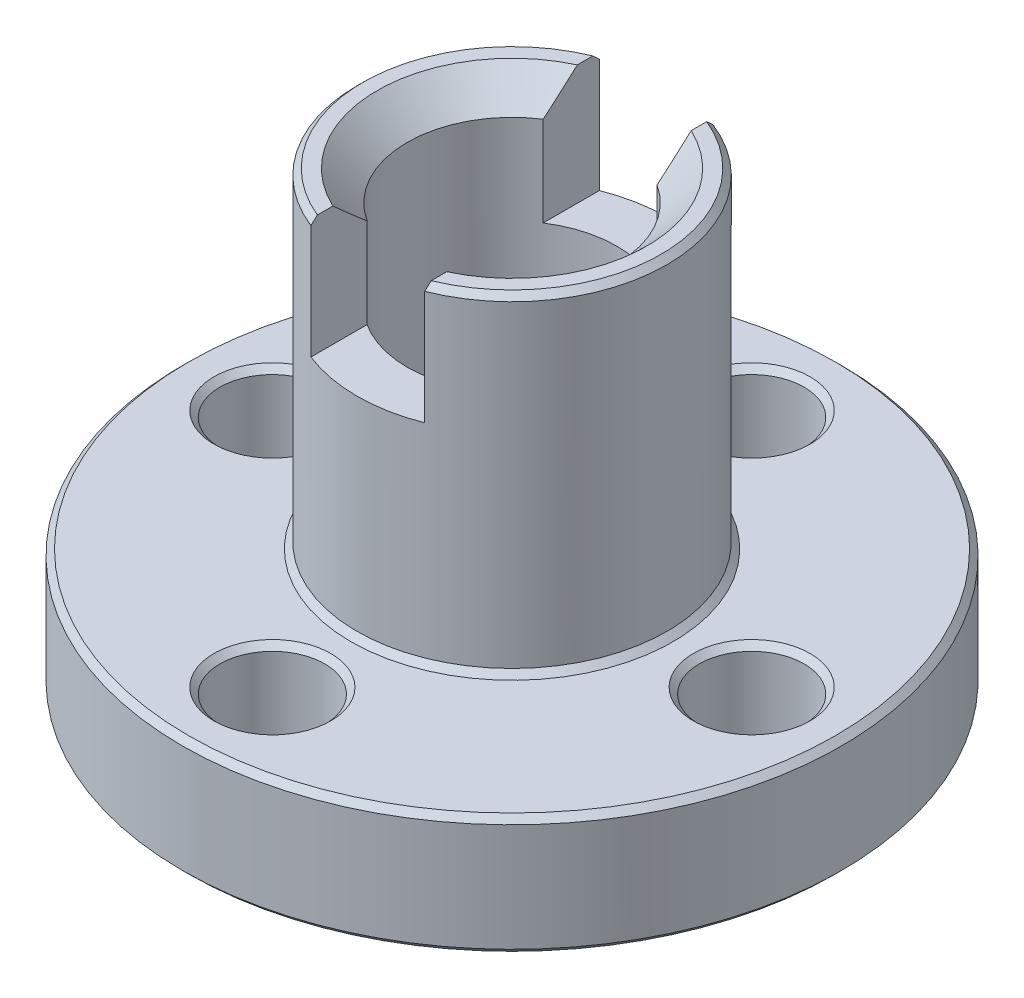
SolidWorks part; units mm, degrees
material "Латунь"
ref_plane "Спереди" through (0, 0, 0) normal (0, 0, 1) x (1, 0, 0)
ref_plane "Сверху" through (0, 0, 0) normal (0, 1, 0) x (1, 0, 0)
ref_plane "Справа" through (0, 0, 0) normal (1, 0, 0) x (0, 0, -1)
sketch "Эскиз2" plane through (0, 0, 0) normal (1, 0, 0) x (0, 0, -1)
  line L0 (0, 0) -> (11, 0)
  line L1 (11, 0) -> (11, 4)
  line L2 (11, 4) -> (5.175, 4)
  line L3 (5.175, 4) -> (5.175, 15)
  line L4 (5.175, 15) -> (0, 15)
  line L5 (0, 15) -> (0, 0)
  line L6 (0, 40.8158) -> (0, -22.7526) construction
  line L7 (3.5, 15) -> (3.5, 0)
  dimension "D1" = 22
  dimension "D2" = 4
  dimension "D3" = 10.35
  dimension "D4" = 15
  dimension "D5" = 7
revolve "Повернуть1" add sketch "Эскиз2" angle 360 about L6 region at (0, 7.5, -3.6677)
sketch "Эскиз3" plane through (0, 0, 0) normal (0, 0, 1) x (1, 0, 0)
  line L0 (0, 16.2105) -> (0, -1.0118) construction
  line L1 (-1.9, 15) -> (1.9, 15)
  line L3 (5.175, 15) -> (-5.175, 15) construction
  line L4 (1.9, 15) -> (1.9, 11)
  line L5 (1.9, 11) -> (-1.9, 11)
  line L6 (-1.9, 11) -> (-1.9, 15)
  point P6 (0, 15)
  dimension "D1" = 3.8
  dimension "D2" = 4
extrude "Вырез-Вытянуть1" cut sketch "Эскиз3" against normal through all both and the other way through all
sketch "Эскиз4" plane through (0, 0, 0) normal (0, -1, 0) x (1, 0, 0)
  line L0 (0, 11.701) -> (0, -11.9582) construction
  circle A0 centre (0, 8) radius 1.75
  circle A1 centre (8, 0) radius 1.75
  circle A2 centre (0, -8) radius 1.75
  circle A3 centre (-8, 0) radius 1.75
  point P14 (0, 0)
  dimension "D2" = 3.5
  dimension "D1" = 8
  dimension "D3" = 4
extrude "Вырез-Вытянуть2" cut sketch "Эскиз4" against normal blind 4
chamfer "Фаска1" distance 1 angle 45 3 edges at (3.5, 15, 0) (-3.5, 15, 0) (0, 0, 3.5)
chamfer "Фаска2" distance 0.2 angle 45 13 edges at (0, 0, -9.75) (0, 4, -9.75) (8, 0, -1.75) (8, 4, -1.75) (-8, 0, -1.75) (-8, 4, -1.75) (0, 0, 6.25) (0, 4, 6.25) (0, 0, 11) (0, 4, 11) (0, 4, 5.175) (5.175, 15, 0) (-5.175, 15, 0)
